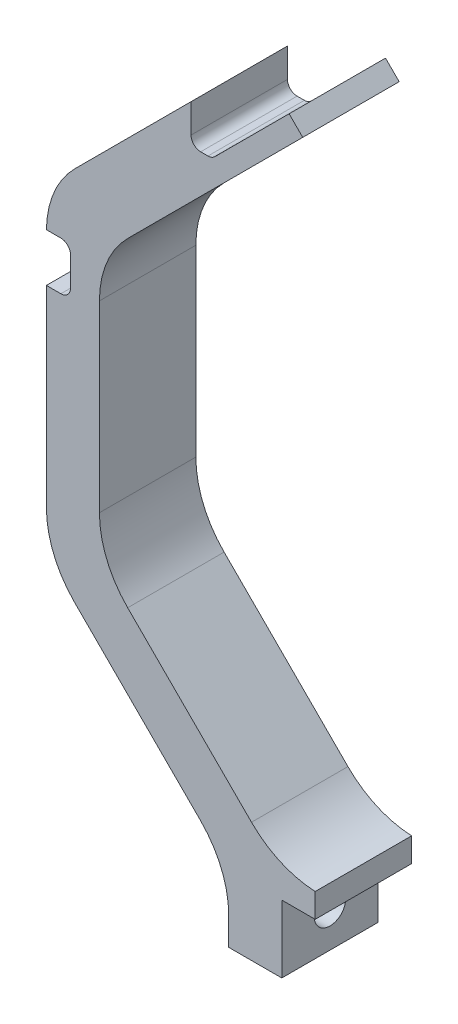
SolidWorks part; units mm, degrees
ref_plane "Piano frontale" through (0, 0, 0) normal (0, 0, 1) x (1, 0, 0)
ref_plane "Piano superiore" through (0, 0, 0) normal (0, 1, 0) x (1, 0, 0)
ref_plane "Piano destro" through (0, 0, 0) normal (1, 0, 0) x (0, 0, -1)
sketch "Schizzo1" plane through (0, 0, 0) normal (0, 0, 1) x (1, 0, 0)
  line L0 (-13.8912, -0.6) -> (-19.3912, -0.6)
  line L1 (-19.3912, -0.6) -> (-19.3912, 6.4)
  line L2 (-19.3912, 6.4) -> (-38.3027, 25.3115)
  line L3 (-38.3027, 25.3115) -> (-38.3027, 58.4)
  line L4 (-38.3027, 58.4) -> (-23.3027, 73.4)
  line L5 (-23.3027, 73.4) -> (-23.3027, 69.4)
  line L6 (-23.3027, 69.4) -> (-21.1311, 69.4)
  line L7 (-21.1311, 69.4) -> (-13.1311, 77.4)
  line L8 (-13.1311, 77.4) -> (-11.7169, 75.9858)
  line L9 (-11.7169, 75.9858) -> (-32.8027, 54.9)
  line L10 (-32.8027, 54.9) -> (-32.8027, 27.5897)
  line L11 (-32.8027, 27.5897) -> (-14.113, 8.9)
  line L12 (-13.8912, 6.4) -> (-13.8912, -0.6)
  line L13 (-23.3027, 69.4) -> (-18.3027, 69.4) construction
  line L14 (-13.8912, 6.4) -> (-10.4277, 6.4)
  line L15 (-10.4277, 6.4) -> (-10.4277, 8.9)
  line L16 (-10.4277, 8.9) -> (-14.113, 8.9)
  line L17 (1.6973, -0.32) -> (1.6973, 43.0665) construction
  dimension "D1" = 70
  dimension "D2" = 5.5
  dimension "D3" = 5.5
  dimension "D4" = 2
  dimension "D5" = 8
  dimension "D6" = 5
  dimension "D7" = 135
  dimension "D8" = 4
  dimension "D9" = 5.5
  dimension "D10" = 15
  dimension "D11" = 7
  dimension "D12" = 2.5
  dimension "D13" = 40
extrude "Estrusione-Estrusione1" add sketch "Schizzo1" along normal mid plane 10
sketch "Schizzo2" plane through (-19.3912, 0, 0) normal (-1, 0, 0) x (0, 0, 1)
  line L0 (5, 6.4) -> (-5, 6.4) construction
  line L6 (-5, 6.4) -> (-5, -0.6) construction
  circle A0 centre (0, 3.2) radius 2.5
  dimension "D2" = 5
  dimension "D1" = 3.2
  dimension "D4" = 5
other "AllineaGruppo1"
extrude "Taglio-Estrusione2" cut sketch "Schizzo2" against normal blind 3.5 contours A0
sketch "Schizzo3" plane through (-19.3912, 0, 0) normal (-1, 0, 0) x (0, 0, 1)
  circle A0 centre (0, 3.2) radius 1.625
  circle A1 centre (0, 3.2) radius 2.5 construction
  dimension "D1" = 3.25
extrude "Taglio-Estrusione3" cut sketch "Schizzo3" against normal blind 10
fillet "Raccordo1" radius 10 6 edges at (-19.3912, 6.4, 0) (-14.113, 8.9, 0) (-32.8027, 27.5897, 0) (-38.3027, 25.3115, 0) (-32.8027, 54.9, 0) (-38.3027, 58.4, 0)
sketch "Schizzo4" plane through (0, 0, -5) normal (0, 0, -1) x (-1, 0, 0)
  line L0 (38.3027, 54.2579) -> (38.3027, 29.4537) construction
  line L1 (38.3027, 54.4) -> (35.8027, 54.4)
  line L2 (38.3027, 54.4) -> (38.3027, 49.4)
  line L3 (38.3027, 49.4) -> (35.8027, 49.4)
  line L4 (35.8027, 54.4) -> (35.8027, 49.4)
  line L5 (21.1311, 69.4) -> (23.3027, 69.4) construction
  dimension "D1" = 5
  dimension "D2" = 2.5
  dimension "D3" = 15
extrude "Taglio-Estrusione4" cut sketch "Schizzo4" against normal blind 10
fillet "Raccordo2" radius 1 4 edges at (-23.3027, 69.4, 0) (-35.8027, 49.4, 0) (-35.8027, 54.4, 0) (-21.1311, 69.4, 0)
sketch "Schizzo5" plane through (-43.8513, 43.8513, 0) normal (0.7071, -0.7071, 0) x (0, 0, -1)
  line L0 (-5, 45.445) -> (5, 45.445) construction
  line L1 (-5, 19.7673) -> (-5, 45.445) construction
  circle A0 centre (0, 41.445) radius 1.625
  dimension "D2" = 3.25
  dimension "D1" = 4
  dimension "D3" = 5
extrude "Taglio-Estrusione5" cut sketch "Schizzo5" against normal blind 10
